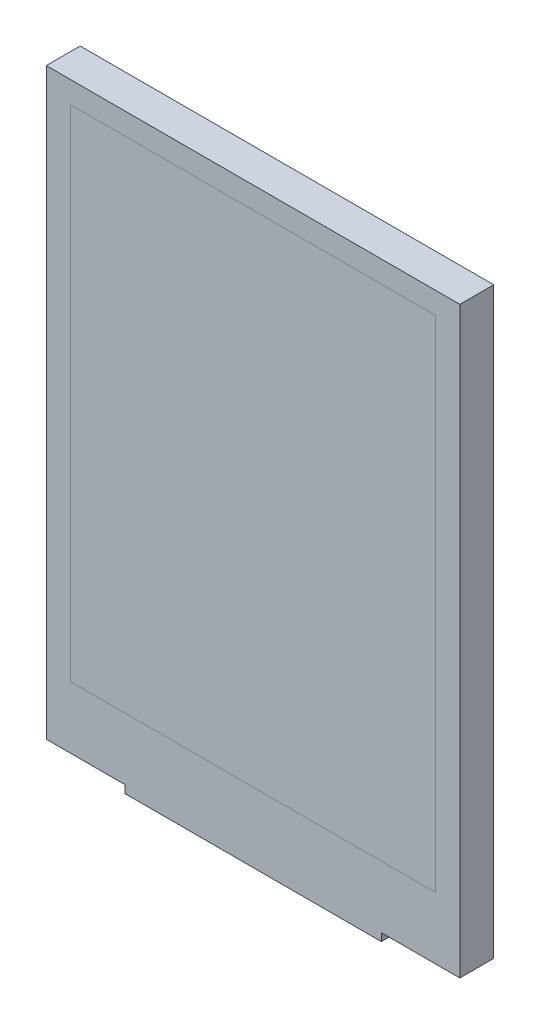
SolidWorks part; units mm, degrees
ref_plane "Front Plane" through (0, 0, 0) normal (0, 0, 1) x (1, 0, 0)
ref_plane "Top Plane" through (0, 0, 0) normal (0, 1, 0) x (1, 0, 0)
ref_plane "Right Plane" through (0, 0, 0) normal (1, 0, 0) x (0, 0, -1)
sketch "Sketch1" plane through (0, 0, 0) normal (0, 0, 1) x (1, 0, 0)
  line L1 (18.86, 25.805) -> (-18.86, 25.805)
  line L2 (18.86, 25.805) -> (18.86, -25.805)
  line L3 (18.86, -25.805) -> (-18.86, -25.805)
  line L4 (-18.86, 25.805) -> (-18.86, -25.805)
  line L5 (0, -25.805) -> (0, 25.805) construction
  line L6 (18.86, 0) -> (-18.86, 0) construction
  line L7 (21.36, 28.055) -> (-21.36, 28.055)
  line L8 (21.36, 28.055) -> (21.36, -32.205)
  line L9 (21.36, -32.205) -> (-21.36, -32.205)
  line L10 (-21.36, 28.055) -> (-21.36, -32.205)
  line L11 (0, -32.205) -> (0, 28.055) construction
  line L12 (21.36, -2.075) -> (-21.36, -2.075) construction
  line L13 (13.25, -33.005) -> (-13.25, -33.005)
  line L14 (13.25, -33.005) -> (13.25, -32.205)
  line L15 (13.25, -32.205) -> (-13.25, -32.205)
  line L16 (-13.25, -33.005) -> (-13.25, -32.205)
  line L17 (0, -32.205) -> (0, -33.005) construction
  line L18 (13.25, -32.605) -> (-13.25, -32.605) construction
  point P0 (0, 0)
  point P4 (0, 0)
  point P10 (0, -32.605)
  dimension "D1" = 51.61
  dimension "D2" = 37.72
  dimension "D3" = 42.72
  dimension "D4" = 2.5
  dimension "D5" = 2.25
  dimension "D6" = 60.26
  dimension "D7" = 0.8
  dimension "D8" = 26.5
extrude "Boss-Extrude1" add sketch "Sketch1" along normal blind 3.5 contours L7 L10 L9 L8 L4 L1 L2 L3 | L16 L13 L14 L9 region at (20.6213, -2.075, 0) region at (0, -32.605, 0)
extrude "Boss-Extrude2" add sketch "Sketch1<3>" along normal up to vertex (3.5 mm away) separate body contours L1 L4 L3 L2 region at (0, 0, 0) up to point (-21.36, 28.055, 3.5)
sketch "Sketch1<3>" plane through (0, 0, 0) normal (0, 0, 1) x (1, 0, 0) same geometry as "Sketch1"
